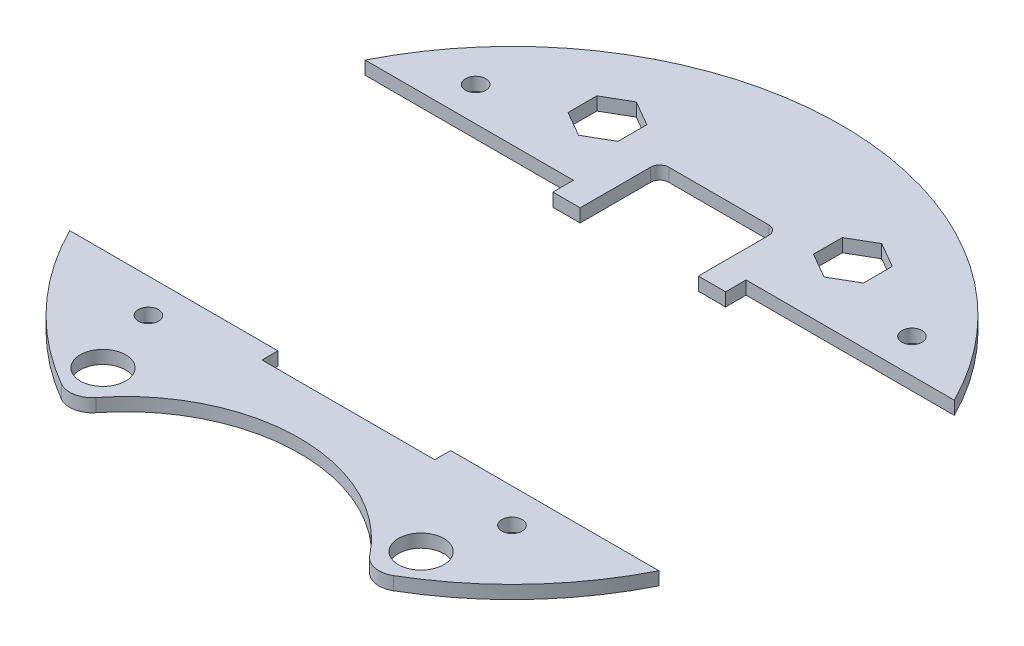
SolidWorks part; units mm, degrees
material "Acrylic (Medium-high impact)"
ref_plane "Front Plane" through (0, 0, 0) normal (0, 0, 1) x (1, 0, 0)
ref_plane "Top Plane" through (0, 0, 0) normal (0, 1, 0) x (1, 0, 0)
ref_plane "Right Plane" through (0, 0, 0) normal (1, 0, 0) x (0, 0, -1)
sketch "Sketch1" plane through (0, 0, 0) normal (0, 1, 0) x (1, 0, 0)
  line L0 (0, -85) -> (-32.4891, -64.8129) construction
  line L1 (0, -85) -> (0, 0) construction
  arc A0 (36.5434, -62.6165) -> (-36.5434, -62.6165) centre (0, 0) ccw
  arc A1 (30.0898, -61.3851) -> (-30.0898, -61.3851) centre (0, -85) ccw
  arc A2 (36.5434, -62.6165) -> (30.0898, -61.3851) centre (34.0231, -58.2982) cw
  arc A3 (-30.0898, -61.3851) -> (-36.5434, -62.6165) centre (-34.0231, -58.2982) cw
  dimension "D1" = 145
  dimension "D2" = 76.5
  dimension "D4" = 5
  dimension "D3" = 85
extrude "Boss-Extrude1" add sketch "Sketch1" along normal blind 2.9
sketch "solenoid placement" plane through (0, 2.9, 0) normal (0, 1, 0) x (1, 0, 0)
  line L4 (-19, -36) -> (19, -36)
  line L5 (-19, 28) -> (-19, -36)
  line L6 (19, 28) -> (-19, 28)
  line L7 (19, -36) -> (19, 28)
  line L8 (-19, -36) -> (19, -36)
  line L9 (-19, 28) -> (-19, -36)
  line L10 (19, 28) -> (-19, 28)
  line L11 (19, -36) -> (19, 28)
  dimension "D1" = 0
extrude "Cut-Extrude1" cut sketch "solenoid placement" against normal through all
sketch "Sketch5" plane through (0, 2.9, 0) normal (0, 1, 0) x (1, 0, 0)
  line L12 (-21.5, 51.1754) -> (-27, 54.3509)
  line L13 (-27, 54.3509) -> (-32.5, 51.1754)
  line L14 (-32.5, 51.1754) -> (-32.5, 44.8246)
  line L15 (-32.5, 44.8246) -> (-27, 41.6491)
  line L16 (-27, 41.6491) -> (-21.5, 44.8246)
  line L17 (-21.5, 44.8246) -> (-21.5, 51.1754)
  line L18 (-21.5, 51.1754) -> (-27, 54.3509)
  line L19 (-27, 54.3509) -> (-32.5, 51.1754)
  line L20 (-32.5, 51.1754) -> (-32.5, 44.8246)
  line L21 (-32.5, 44.8246) -> (-27, 41.6491)
  line L22 (-27, 41.6491) -> (-21.5, 44.8246)
  line L23 (-21.5, 44.8246) -> (-21.5, 51.1754)
  line L24 (21.5, 51.1754) -> (21.5, 44.8246)
  line L25 (21.5, 44.8246) -> (27, 41.6491)
  line L26 (27, 41.6491) -> (32.5, 44.8246)
  line L27 (32.5, 44.8246) -> (32.5, 51.1754)
  line L28 (32.5, 51.1754) -> (27, 54.3509)
  line L29 (27, 54.3509) -> (21.5, 51.1754)
  line L42 (21.5, 51.1754) -> (21.5, 44.8246)
  line L43 (21.5, 44.8246) -> (27, 41.6491)
  line L44 (27, 41.6491) -> (32.5, 44.8246)
  line L45 (32.5, 44.8246) -> (32.5, 51.1754)
  line L46 (32.5, 51.1754) -> (27, 54.3509)
  line L47 (27, 54.3509) -> (21.5, 51.1754)
  dimension "D1" = 0
  dimension "D2" = 0
extrude "Cut-Extrude5" cut sketch "Sketch5" against normal through all
sketch "Sketch6" plane through (0, 2.9, 0) normal (0, 1, 0) x (1, 0, 0)
  circle A0 centre (48, 40) radius 2.225
  circle A1 centre (40, -40) radius 2.4
  circle A2 centre (40, -40) radius 2.4 construction
  circle A3 centre (-40, -40) radius 2.4
  circle A4 centre (-40, -40) radius 2.4 construction
  circle A5 centre (48, 40) radius 2.4
  circle A6 centre (48, 40) radius 2.4 construction
  circle A7 centre (-48, 40) radius 2.4
  circle A8 centre (-48, 40) radius 2.4 construction
  circle A9 centre (-48, 40) radius 2.225
  circle A10 centre (40, -40) radius 2.225
  circle A11 centre (-40, -40) radius 2.225
  dimension "D5" = 4.45
extrude "Cut-Extrude6" cut sketch "Sketch6" against normal through all
sketch "Sketch3" plane through (0, 2.9, 0) normal (0, 1, 0) x (1, 0, 0)
  line L0 (-19, 28) -> (-19, 32.5)
  line L1 (72.5, -32.5) -> (-72.5, -32.5)
  line L2 (72.5, -32.5) -> (72.5, 32.5)
  line L3 (72.5, 32.5) -> (19, 32.5)
  line L4 (-72.5, -32.5) -> (-72.5, 32.5)
  line L5 (72.5, -32.5) -> (-72.5, 32.5) construction
  line L6 (72.5, 32.5) -> (-72.5, -32.5) construction
  line L7 (-19, 28) -> (19, 28)
  line L8 (19, 28) -> (19, 32.5)
  line L9 (-19, 32.5) -> (-72.5, 32.5)
  line L10 (-19, 28) -> (-19, -36) construction
  arc A0 (36.5434, -62.6165) -> (-36.5434, -62.6165) centre (0, 0) ccw construction
  point P0 (0, 0)
  dimension "D1" = 65
extrude "Cut-Extrude3" cut sketch "Sketch3" against normal through all
sketch "Sketch7" plane through (0, 2.9, 0) normal (0, 1, 0) x (1, 0, 0)
  line L8 (13, 28) -> (13, 43.5)
  line L9 (-13, 28) -> (13, 28)
  line L10 (-13, 43.5) -> (-13, 28)
  line L11 (11, 45.5) -> (-11, 45.5)
  line L28 (13, 28) -> (13, 43.5)
  line L29 (-13, 28) -> (13, 28)
  line L30 (-13, 43.5) -> (-13, 28)
  line L31 (11, 45.5) -> (-11, 45.5)
  arc A4 (-11, 45.5) -> (-13, 43.5) centre (-11, 43.5) ccw
  arc A5 (13, 43.5) -> (11, 45.5) centre (11, 43.5) ccw
  arc A14 (-11, 45.5) -> (-13, 43.5) centre (-11, 43.5) ccw
  arc A15 (13, 43.5) -> (11, 45.5) centre (11, 43.5) ccw
  dimension "D1" = 0
extrude "Cut-Extrude7" cut sketch "Sketch7" against normal through all
sketch "Sketch8" plane through (0, 2.9, 0) normal (0, 1, 0) x (1, 0, 0)
  circle A1 centre (35, -55) radius 5
  circle A2 centre (35, -55) radius 5
  circle A3 centre (-35, -55) radius 5
  circle A4 centre (-35, -55) radius 5
  dimension "D1" = 0
  dimension "D2" = 0
extrude "Cut-Extrude8" cut sketch "Sketch8" against normal through all
equation "\"smallPulleyTeeth\"= 15"
equation "\"largePulleyTeeth\"= 30"
equation "\"eighthThick\"= 2.9mm"
equation "\"sixteenthThick\" = 1.7mm"
equation "\"quarterThick\"=6.0mm"
equation "\"OD\" = 145mm"
equation "\"puckAngle\" = 60.5deg"
equation "\"D1@Sketch1\"=\"OD\""
equation "\"puckDiam\" = 76.5mm"
equation "\"D2@Sketch1\"=\"puckDiam\""
equation "\"D1@Boss-Extrude1\"=\"eighthThick\""
equation "\"axlePress\" = 5.9mm"
equation "\"press\" = 0.2mm"
equation "\"wheelClear\" = 0.3mm"
equation "\"10-32clear\" = 4.8mm"
equation "\"6-32clear\" = 3.3mm"
equation "\"8-32clear\" = 4.0mm"
equation "\"wheelHeight\" = 22mm"
equation "\"wheelWell\" = 65mm"
equation "\"D1@Sketch3\"=\"wheelWell\""
equation "\"puckDist\" = 85mm"
equation "\"scoopFillet\" = 5mm"
equation "\"4-40clear\" = 3.0mm"
equation "\"D3@Sketch1\"=\"puckDist\""
equation "\"D4@Sketch1\"=\"scoopFillet\""
equation "\"10-32tap\" = 4.45mm"
equation "\"D5@Sketch6\"=\"10-32tap\""
